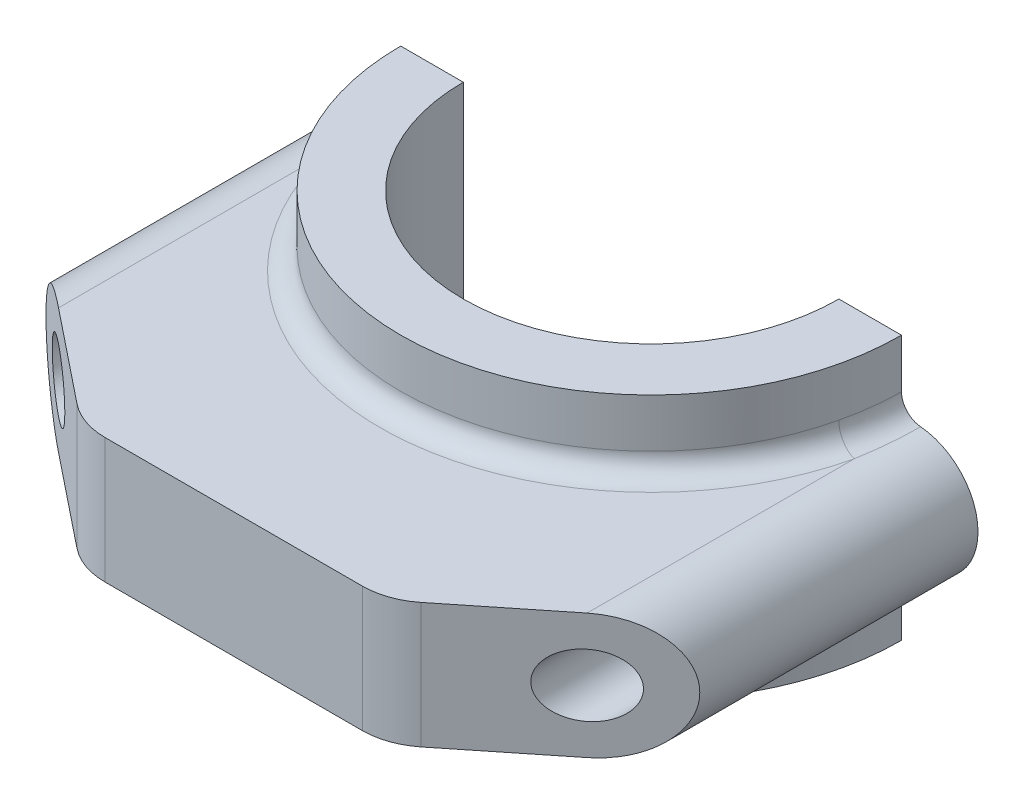
SolidWorks part; units mm, degrees
ref_plane "Front Plane" through (0, 0, 0) normal (0, 0, 1) x (1, 0, 0)
ref_plane "Top Plane" through (0, 0, 0) normal (0, 1, 0) x (1, 0, 0)
ref_plane "Right Plane" through (0, 0, 0) normal (1, 0, 0) x (0, 0, -1)
sketch "Sketch1" plane through (0, 0, 0) normal (0, 1, 0) x (1, 0, 0)
  line L0 (-27, 0) -> (-36, 0)
  line L1 (27, 0) -> (36, 0)
  line L2 (-47, 0) -> (-47, -40)
  line L3 (-47, -40) -> (-24.7391, -57.8087)
  line L4 (-18.4922, -60) -> (18.4922, -60)
  line L5 (24.7391, -57.8087) -> (47, -40)
  line L6 (47, -40) -> (47, 0)
  line L7 (0, 0) -> (0, 19.3271) construction
  line L8 (-47, 0) -> (-36, 0)
  line L9 (47, 0) -> (36, 0)
  arc A0 (-27, 0) -> (27, 0) centre (0, 0) ccw
  arc A1 (-36, 0) -> (36, 0) centre (0, 0) ccw
  arc A2 (18.4922, -60) -> (24.7391, -57.8087) centre (18.4922, -50) ccw
  arc A3 (-24.7391, -57.8087) -> (-18.4922, -60) centre (-18.4922, -50) ccw
  point P22 (-22, -60)
  dimension "D1" = 27
  dimension "D2" = 36
  dimension "D7" = 10
  dimension "D3" = 94
  dimension "D4" = 20
  dimension "D5" = 25
  dimension "D6" = 60
extrude "Boss-Extrude1" add sketch "Sketch1" along normal mid plane 38 contours L0 A1 L1 A0 region at (0, 0, 27.805)
extrude "Boss-Extrude2" add sketch "Sketch1<3>" along normal mid plane 18 contours L3 A3 L4 A2 L5 L6 L9 A1 L8 L2 region at (0, 0, 37.1152)
sketch "Sketch1<3>" plane through (0, 0, 0) normal (0, 1, 0) x (1, 0, 0) same geometry as "Sketch1"
fillet "Fillet1" 2 edges at (-47, 9, 20) (-47, -9, 20) type full round first side face at (0, 9, 35.2681) second side face at (0, -9, 35.2681) middle face at (-47, 0, 20)
fillet "Fillet2" 2 edges at (47, -9, 20) (47, 9, 20) type full round first side face at (1.8, -9, 35.9881) second side face at (1.8, 9, 35.9881) middle face at (47, 0, 20)
sketch "Sketch2" plane through (0, 0, 0) normal (0, 0, -1) x (-1, 0, 0)
  line L0 (0, 0) -> (0, -13.9841) construction
  circle A0 centre (-38, 0) radius 4.5
  circle A1 centre (38, 0) radius 4.5
  dimension "D1" = 9
extrude "Cut-Extrude1" cut sketch "Sketch2" against normal up to next
fillet "Fillet3" radius 3 2 edges at (0, 9, 36) (0, -9, 36)
